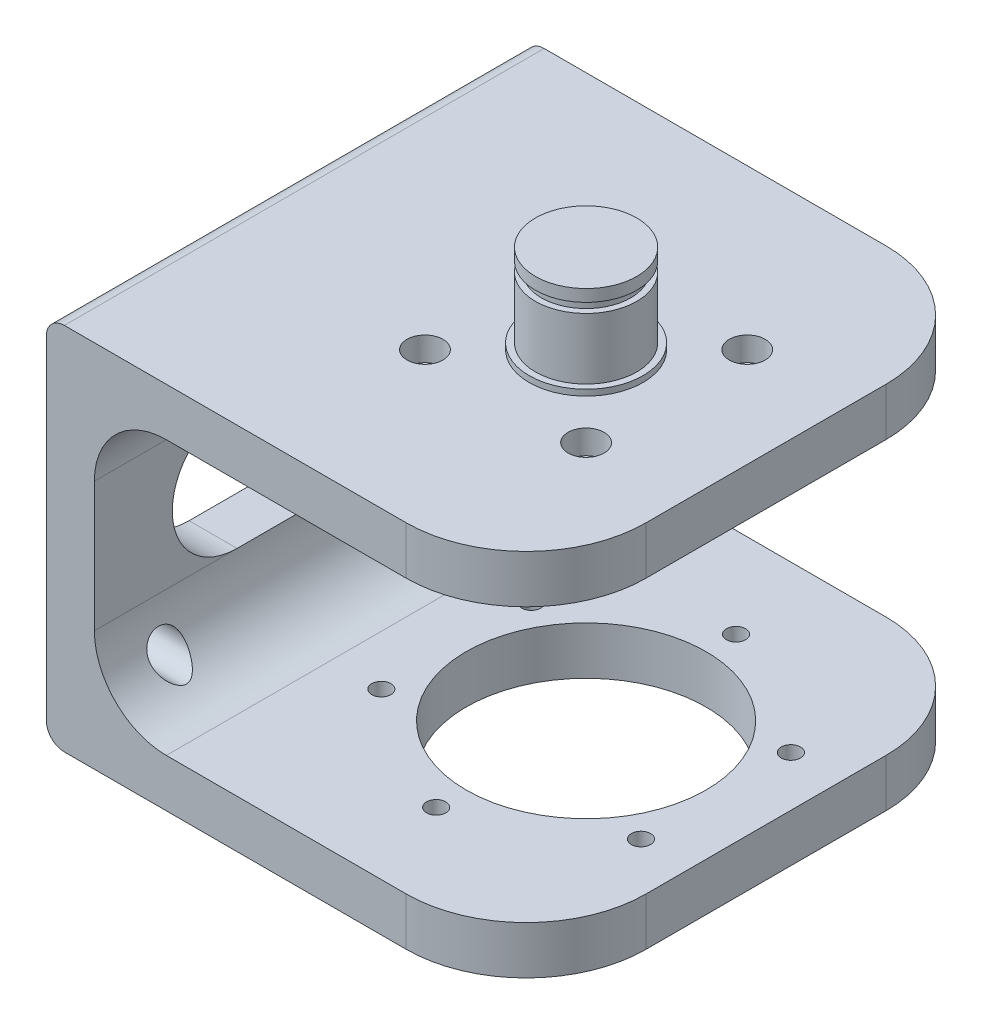
SolidWorks part; units mm, degrees
material "PETG-CF"
ref_plane "Front Plane" through (0, 0, 0) normal (0, 0, 1) x (1, 0, 0)
ref_plane "Top Plane" through (0, 0, 0) normal (0, 1, 0) x (1, 0, 0)
ref_plane "Right Plane" through (0, 0, 0) normal (1, 0, 0) x (0, 0, -1)
sketch "草图1" plane through (0, 0, 0) normal (0, 1, 0) x (1, 0, 0)
  line L1 (40, -40) -> (-40, -40)
  line L2 (40, -40) -> (40, 40)
  line L3 (40, 40) -> (-40, 40)
  line L4 (-40, -40) -> (-40, 40)
  line L5 (40, -40) -> (-40, 40) construction
  line L6 (40, 40) -> (-40, -40) construction
  point P0 (0, 0)
  dimension "D1" = 80
  dimension "D2" = 80
extrude "凸台-拉伸1" add sketch "草图1" along normal blind 8
sketch "草图2" plane through (0, 8, 0) normal (0, 1, 0) x (1, 0, 0)
  line L0 (-40, -40) -> (40, -40) construction
  line L1 (-32, -40) -> (-40, -40)
  line L2 (-32, -40) -> (-32, 40)
  line L3 (-32, 40) -> (-40, 40)
  line L4 (-40, -40) -> (-40, 40)
  line L5 (-32, -40) -> (-40, 40) construction
  line L6 (-32, 40) -> (-40, -40) construction
  point P0 (-36, 0)
  dimension "D1" = 8
extrude "凸台-拉伸2" add sketch "草图2" along normal blind 53.6
sketch "草图5" plane through (-32, 0, 0) normal (1, 0, 0) x (0, 0, -1)
  line L0 (-40, 61.6) -> (-40, 8) construction
  line L1 (40, 53.6) -> (-40, 53.6)
  line L2 (40, 53.6) -> (40, 61.6)
  line L3 (40, 61.6) -> (-40, 61.6)
  line L4 (-40, 53.6) -> (-40, 61.6)
  line L5 (40, 53.6) -> (-40, 61.6) construction
  line L6 (40, 61.6) -> (-40, 53.6) construction
  line L7 (40, 61.6) -> (40, 8) construction
  line L9 (-40, 61.6) -> (40, 61.6) construction
  point P0 (0, 57.6)
  dimension "D1" = 8
extrude "凸台-拉伸3" add sketch "草图5" along normal through all
sketch "草图4" plane through (0, 8, 0) normal (0, 1, 0) x (1, 0, 0)
  line L0 (-40, 40) -> (-40, -40) construction
  line L2 (40, -40) -> (40, 40) construction
  circle A0 centre (10, 0) radius 25 construction
  circle A1 centre (10, 25) radius 1.6
  circle A2 centre (-11.6506, 12.5) radius 1.6
  circle A3 centre (-11.6506, -12.5) radius 1.6
  circle A4 centre (10, -25) radius 1.6
  circle A5 centre (10, 0) radius 20
  circle A6 centre (31.6506, -12.5) radius 1.6
  circle A7 centre (31.6506, 12.5) radius 1.6
  point P2 (10, 0)
  point P17 (10, 0)
  point P22 (-40, 0)
  dimension "D3" = 50
  dimension "D4" = 3.2
  dimension "D6" = 40
  dimension "D1" = 30
  dimension "D5" = 6
extrude "切除-拉伸1" cut sketch "草图4" against normal through all contours A5 | A2 | A1 | A4 | A3 | A7 | A6
sketch "草图7" plane through (0, 61.6, 0) normal (0, 1, 0) x (1, 0, 0)
  line L0 (40, 40) -> (40, -40) construction
  line L2 (40, 40) -> (40, -40) construction
  line L3 (10, 0) -> (-3.435, 13.435) construction
  line L4 (10, 0) -> (10, 19) construction
  circle A0 centre (10, 0) radius 19 construction
  circle A5 centre (-3.435, 13.435) radius 1.6
  circle A6 centre (23.435, 13.435) radius 1.6
  circle A7 centre (23.435, -13.435) radius 1.6
  circle A8 centre (-3.435, -13.435) radius 1.6
  point P2 (0, 0)
  point P10 (40, 0)
  point P11 (10, 0)
  point P18 (10, 0)
  point P20 (10, 0)
  dimension "D1" = 38
  dimension "D4" = 45
  dimension "D5" = 3.2
  dimension "D3" = 30
  dimension "D6" = 4
extrude "切除-拉伸3" cut sketch "草图7" against normal up to next
fillet "圆角3" radius 20 4 edges at (40, 4, 40) (40, 4, -40) (40, 57.6, -40) (40, 57.6, 40)
fillet "圆角4" radius 12 2 edges at (-32, 8, 0) (-32, 53.6, 0)
fillet "圆角5" radius 3 2 edges at (-40, 0, 0) (-40, 61.6, 0)
sketch "草图6" plane through (-40, 0, 0) normal (-1, 0, 0) x (0, 0, 1)
  line L0 (-40, 61.6) -> (40, 61.6) construction
  line L1 (30, 13) -> (-30, 13) construction
  line L2 (30, 13) -> (30, 48.6) construction
  line L3 (30, 48.6) -> (-30, 48.6) construction
  line L4 (-30, 13) -> (-30, 48.6) construction
  line L5 (30, 13) -> (-30, 48.6) construction
  line L6 (30, 48.6) -> (-30, 13) construction
  line L7 (40, 0) -> (-40, 0) construction
  line L8 (40, 58.6) -> (40, 3) construction
  line L9 (-40, 58.6) -> (-40, 3) construction
  line L10 (-30, 30.8) -> (30, 30.8) construction
  line L11 (0, 13) -> (0, 48.6) construction
  circle A0 centre (-30, 48.6) radius 1.6
  circle A1 centre (30, 48.6) radius 1.6
  circle A2 centre (30, 13) radius 1.6
  circle A3 centre (-30, 13) radius 1.6
  point P0 (0, 30.8)
  dimension "D5" = 3.2
  dimension "D1" = 13
  dimension "D2" = 13
  dimension "D3" = 10
  dimension "D4" = 10
extrude "切除-拉伸2" cut sketch "草图6" against normal through all
sketch "草图8" plane through (0, 61.6, 0) normal (0, 1, 0) x (1, 0, 0)
  circle A0 centre (10, 0) radius 8.45
  dimension "D1" = 16.9
extrude "凸台-拉伸4" add sketch "草图8" along normal blind 14.8
ref_plane "基准面1" through (0, 74.4, 0) normal (0, 1, 0) x (1, 0, 0)
sketch "草图10" plane through (0, 74.4, 0) normal (0, 1, 0) x (1, 0, 0)
  circle A0 centre (10, 0) radius 8.45
  circle A1 centre (10, 0) radius 7.45
  dimension "D1" = 14.9
extrude "切除-拉伸4" cut sketch "草图10" against normal blind 1.6
ref_plane "基准面2" through (-36, 0, 0) normal (-1, 0, 0) x (0, 0, 1)
sketch "草图12" plane through (-36, 0, 0) normal (-1, 0, 0) x (0, 0, 1)
  line L0 (-40, 30.8) -> (40, 30.8) construction
  line L1 (-40, 58.6) -> (-40, 3) construction
  line L2 (40, 58.6) -> (40, 3) construction
  line L3 (0, 61.6) -> (0, 3) construction
  line L4 (8.45, 61.6) -> (-8.45, 61.6) construction
  line L5 (-40, 3) -> (40, 3) construction
  circle A0 centre (-30, 48.6) radius 3
  circle A1 centre (30, 48.6) radius 3
  circle A2 centre (30, 13) radius 3
  circle A3 centre (-30, 13) radius 3
  dimension "D1" = 6
extrude "切除-拉伸5" cut sketch "草图12" against normal up to next
sketch "草图14" plane through (0, 61.6, 0) normal (0, 1, 0) x (1, 0, 0)
  circle A0 centre (-3.435, 13.435) radius 3
  circle A1 centre (23.435, 13.435) radius 3
  circle A2 centre (23.435, -13.435) radius 3
  circle A3 centre (-3.435, -13.435) radius 3
  point P12 (10, 0)
  dimension "D1" = 6
  dimension "D2" = 4
sketch "Sketch1" plane through (-32, 0, 0) normal (1, 0, 0) x (0, 0, -1)
  line L0 (16.2, 30.8) -> (-16.2, 30.8) construction
  line L1 (16.2, 20) -> (-16.2, 20)
  line L2 (16.2, 41.6) -> (-16.2, 41.6)
  line L3 (40, 41.6) -> (40, 20) construction
  line L4 (20, 61.6) -> (-20, 61.6) construction
  line L5 (40, 41.6) -> (-40, 41.6) construction
  arc A0 (16.2, 20) -> (16.2, 41.6) centre (16.2, 30.8) ccw
  arc A1 (-16.2, 41.6) -> (-16.2, 20) centre (-16.2, 30.8) ccw
  point P2 (0, 30.8)
  point P7 (0, 30.8091)
  point P8 (0, 0)
  point P9 (0, 0)
  point P12 (40, 30.8)
  point P15 (0, 61.6)
  point P18 (27, 30.8)
  dimension "D1" = 13
extrude "Cut-Extrude1" cut sketch "Sketch1" against normal through all
extrude "切除-拉伸6" cut sketch "草图14" against normal blind 4
sketch "草图15" plane through (0, 0, 0) normal (0, -1, 0) x (1, 0, 0)
  circle A0 centre (-11.6506, 12.5) radius 3
  circle A1 centre (10, 25) radius 3
  circle A2 centre (31.6506, 12.5) radius 3
  circle A3 centre (31.6506, -12.5) radius 3
  circle A4 centre (10, -25) radius 3
  circle A5 centre (-11.6506, -12.5) radius 3
  point P15 (10, 0)
  dimension "D1" = 6
  dimension "D2" = 6
extrude "切除-拉伸7" cut sketch "草图15" against normal blind 4
sketch "草图16" plane through (0, 61.6, 0) normal (0, 1, 0) x (1, 0, 0)
  circle A0 centre (10, 0) radius 9.5
  dimension "D1" = 19
extrude "凸台-拉伸5" add sketch "草图16" along normal blind 1
